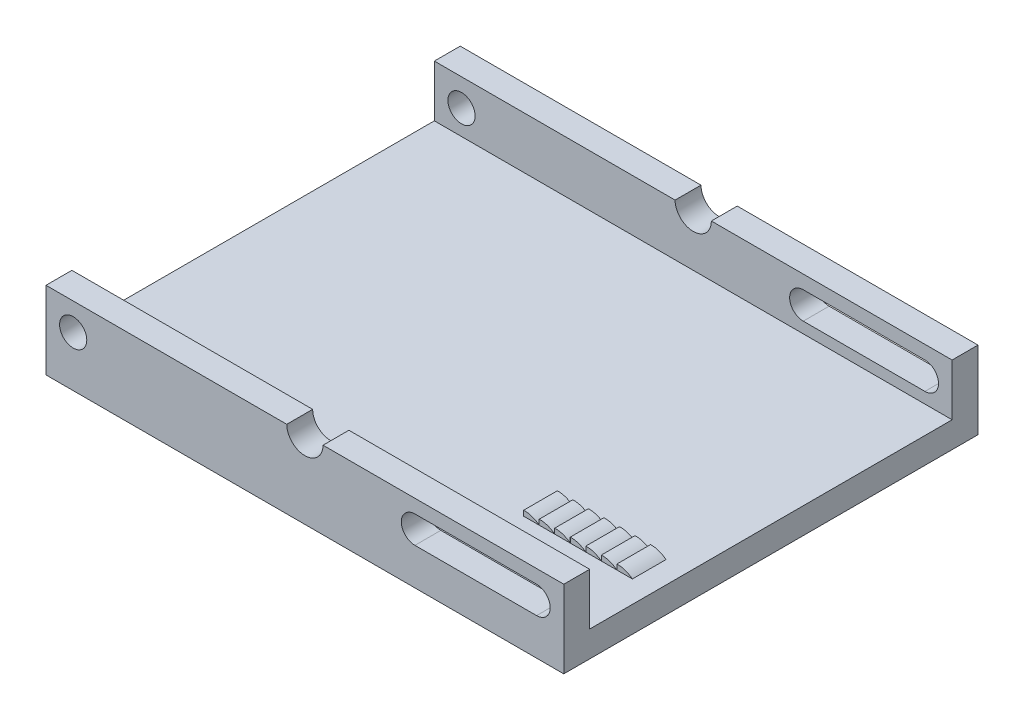
SolidWorks part; units mm, degrees
ref_plane "Vorne" through (0, 0, 0) normal (0, 0, 1) x (1, 0, 0)
ref_plane "Oben" through (0, 0, 0) normal (0, 1, 0) x (1, 0, 0)
ref_plane "Seite" through (0, 0, 0) normal (1, 0, 0) x (0, 0, -1)
sketch "Skizze9" plane through (0, 0, 0) normal (1, 0, 0) x (0, 0, -1)
  line L0 (-80, 30) -> (-80, 0)
  line L1 (-80, 0) -> (80, 0)
  line L2 (80, 0) -> (80, 30)
  line L3 (80, 30) -> (70, 30)
  line L4 (70, 30) -> (70, 10)
  line L5 (70, 10) -> (-70, 10)
  line L6 (-70, 10) -> (-70, 30)
  line L7 (-70, 30) -> (-80, 30)
  line L8 (0, 0) -> (0, 10) construction
  dimension "B" = 160
  dimension "D3" = 30
extrude "Aufsatz-Linear austragen3" add sketch "Skizze9" along normal mid plane 200
sketch "Skizze10" plane through (0, 0, 80) normal (0, 0, 1) x (1, 0, 0)
  line L0 (42.5, 24.75) -> (89.5, 24.75)
  line L2 (89.5, 14.25) -> (42.5, 14.25)
  line L4 (-100, 30) -> (-100, 0) construction
  line L5 (100, 30) -> (-100, 30) construction
  line L6 (100, 30) -> (100, 0) construction
  circle A0 centre (-89.5, 19.5) radius 5.25
  arc A1 (42.5, 24.75) -> (42.5, 14.25) centre (42.5, 19.5) ccw
  arc A2 (89.5, 14.25) -> (89.5, 24.75) centre (89.5, 19.5) ccw
  dimension "D2" = 10.5
  dimension "D1" = 10.5
  dimension "D3" = 10.5
  dimension "D4" = 10.5
  dimension "D5" = 47
extrude "Schnitt-Linear austragen1" cut sketch "Skizze10" against normal through all both and the other way through all
sketch "Skizze12" plane through (0, 0, 0) normal (0, 0, 1) x (1, 0, 0)
  line L0 (100, 30) -> (-100, 30) construction
  line L1 (-7, 30) -> (7, 30)
  arc A0 (-7, 30) -> (7, 30) centre (0, 30) ccw
  dimension "D1" = 7
extrude "Schnitt-Linear austragen2" cut sketch "Skizze12" against normal through all both and the other way through all
sketch "Skizze18" plane through (0, 0, 0) normal (0, 0, -1) x (-1, 0, 0)
  line L1 (-49.5, 10) -> (-55.5, 10)
  line L37 (-49.5, 12) -> (-49.5, 10)
  line L42 (-100, 10) -> (100, 10) construction
  line L44 (-55.5, 10) -> (-61.5, 10) [skipped]
  line L47 (-61.5, 10) -> (-67.5, 10) [skipped]
  line L48 (-67.5, 10) -> (-73.5, 10) [skipped]
  line L50 (-73.5, 10) -> (-79.5, 10) [skipped]
  line L52 (-85.5, 10) -> (-91.5, 10) [skipped]
  line L53 (-79.5, 10) -> (-85.5, 10) [skipped]
  line L56 (-91.5, 10) -> (-97.5, 10) [skipped]
  line L58 (-97.5, 10) -> (-103.5, 10) [skipped]
  line L60 (-103.5, 10) -> (-109.5, 10) [skipped]
  line L63 (-109.5, 10) -> (-115.5, 10) [skipped]
  line L64 (-115.5, 10) -> (-121.5, 10) [skipped]
  arc A0 (-42.5, 14.25) -> (-42.5, 24.75) centre (-42.5, 19.5) ccw construction
  spline S0 degree 2 poles (-55.5, 10) (-52.6677, 12.1247) (-49.5, 12) knots 0 0 0 0.477298 0.477298 0.477298
  dimension "D2" = 2
  dimension "D3" = 7
  dimension "D4" = 12
  dimension "D5" = 6
extrude "Aufsatz-Linear austragen4" add sketch "Skizze18" along direction (0, 0, 1) on the side against the normal blind 45
pattern_linear "Lineares Muster1" count 7 spacing 6 along (1, 0, 0) of "Aufsatz-Linear austragen4"
sketch "Skizze19" plane through (0, 0, 0) normal (0, 0, 1) x (1, 0, 0)
  line L0 (-100, 30) -> (-100, 0) construction
  line L1 (100, 30) -> (-100, 30)
  line L2 (100, 30) -> (100, 10)
  line L3 (100, 10) -> (-100, 10)
  line L4 (-100, 30) -> (-100, 10)
  line L5 (0, 10) -> (0, 30) construction
  line L6 (100, 20) -> (-100, 20) construction
  line L7 (100, 10) -> (-100, 10) construction
  point P660 (0, 20)
extrude "Schnitt-Linear austragen3" cut sketch "Skizze19" along normal blind 32
equation "\"Basis_Breite\" =160"
equation "\"B@Skizze9\"= \"Basis_Breite\""
equation "\"D3@Skizze9\" = \"Basis_höhe\"'Höhe"
equation "\"Basis_höhe\"= 30"
equation "\"Basis_Dicke\"= 10"
equation "\"D2@Skizze9\"= \"Basis_Dicke\""
equation "\"Loch\"= 10.5"
equation "\"D2@Skizze10\"= \"Loch\""
equation "\"D1@Skizze10\"= \"Loch\""
equation "\"D3@Skizze10\"= \"Loch\""
